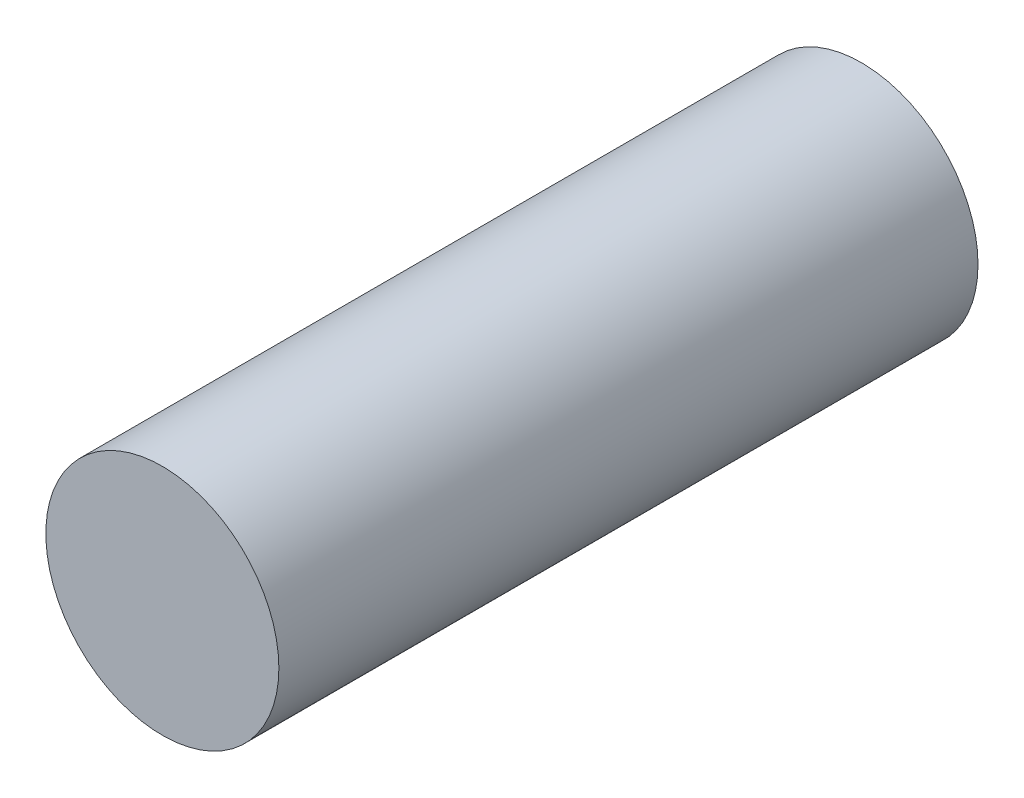
SolidWorks part; units mm, degrees
ref_plane "Plan de face" through (0, 0, 0) normal (0, 0, 1) x (1, 0, 0)
ref_plane "Plan de dessus" through (0, 0, 0) normal (0, 1, 0) x (1, 0, 0)
ref_plane "Plan de droite" through (0, 0, 0) normal (1, 0, 0) x (0, 0, -1)
sketch "Esquisse2" plane through (0, 0, 0) normal (0, 0, 1) x (1, 0, 0)
  circle A0 centre (41.0507, 36.4788) radius 50
  dimension "D1" = 100
extrude "Boss.-Extru.1" add sketch "Esquisse2" along normal blind 300
